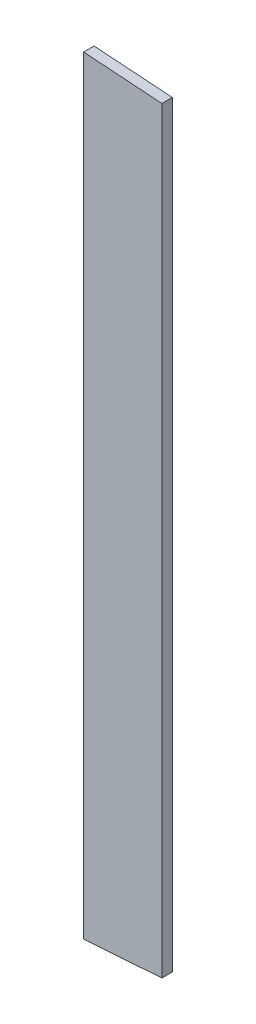
SolidWorks part; units mm, degrees
ref_plane "Front Plane" through (0, 0, 0) normal (0, 0, 1) x (1, 0, 0)
ref_plane "Top Plane" through (0, 0, 0) normal (0, 1, 0) x (1, 0, 0)
ref_plane "Right Plane" through (0, 0, 0) normal (1, 0, 0) x (0, 0, -1)
sketch "Sketch1" plane through (0, 0, 3242.7) normal (0, 0, 1) x (1, 0, 0)
  line L0 (-49.7697, 346.1083) -> (-64.7697, 345.0594)
  line L1 (-140.9262, 339.734) -> (58.5866, 353.6853) construction
  line L2 (-64.7697, 345.0594) -> (-64.7697, 492.4158)
  line L3 (58.5866, 483.7899) -> (-140.9262, 497.7412) construction
  line L4 (-64.7697, 492.4158) -> (-49.7697, 491.3669)
  line L5 (-49.7697, 491.3669) -> (-49.7697, 346.1083)
  dimension "D1" = 15
extrude "Boss-Extrude1" add sketch "Sketch1" along normal blind 2
ref_plane "Plane1" through (-57.2697, 0, 0) normal (1, 0, 0) x (0, 0, -1)
